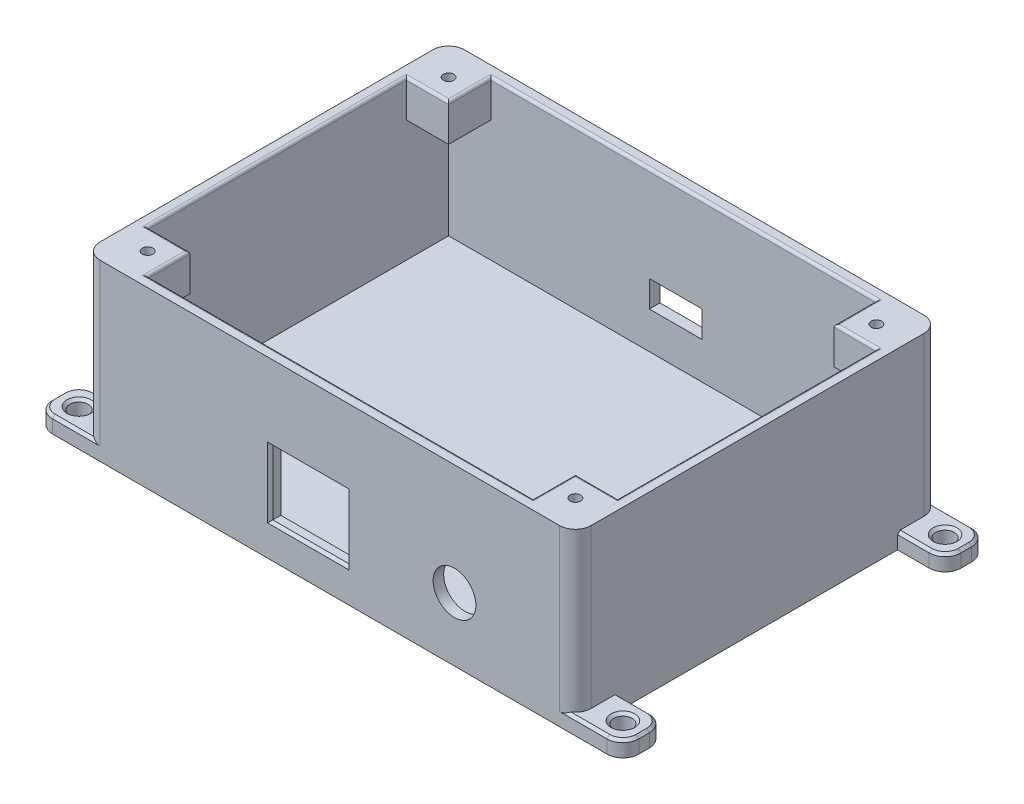
SolidWorks part; units mm, degrees
ref_plane "Front Plane" through (0, 0, 0) normal (0, 0, 1) x (1, 0, 0)
ref_plane "Top Plane" through (0, 0, 0) normal (0, 1, 0) x (1, 0, 0)
ref_plane "Right Plane" through (0, 0, 0) normal (1, 0, 0) x (0, 0, -1)
sketch "Sketch1" plane through (0, 28.7068, 0) normal (0, -1, 0) x (-1, 0, 0)
  line L0 (-31.2305, -86.7531) -> (22.7695, -86.7531) construction
  line L1 (27.7695, -88.7531) -> (-65.2305, -88.7531)
  line L2 (27.7695, -80.7531) -> (27.7695, -27.7531)
  line L3 (27.7695, -19.7531) -> (-65.2305, -19.7531)
  line L4 (-65.2305, -80.7531) -> (-65.2305, -27.7531)
  line L5 (-43.3805, -21.7531) -> (-49.7305, -21.7531) construction
  line L6 (22.7695, -86.7531) -> (22.7695, -23.7531) construction
  line L7 (-62.2305, -23.5531) -> (-62.2305, -59.7531) construction
  line L8 (-18.7305, -19.7531) -> (-18.7305, -88.7531) construction
  line L9 (27.7695, -19.7531) -> (33.7695, -19.7531)
  line L11 (27.7695, -27.7531) -> (33.7695, -27.7531)
  line L12 (36.7695, -22.7531) -> (36.7695, -24.7531)
  line L13 (-65.2305, -54.2531) -> (27.7695, -54.2531) construction
  line L14 (-74.2305, -22.7531) -> (-74.2305, -24.7531)
  line L15 (-65.2305, -27.7531) -> (-71.2305, -27.7531)
  line L16 (-65.2305, -19.7531) -> (-71.2305, -19.7531)
  line L17 (-65.2305, -88.7531) -> (-71.2305, -88.7531)
  line L18 (-65.2305, -80.7531) -> (-71.2305, -80.7531)
  line L19 (-74.2305, -85.7531) -> (-74.2305, -83.7531)
  line L20 (36.7695, -85.7531) -> (36.7695, -83.7531)
  line L21 (27.7695, -80.7531) -> (33.7695, -80.7531)
  line L22 (27.7695, -88.7531) -> (33.7695, -88.7531)
  arc A0 (33.7695, -27.7531) -> (36.7695, -24.7531) centre (33.7695, -24.7531) ccw
  arc A1 (33.7695, -19.7531) -> (36.7695, -22.7531) centre (33.7695, -22.7531) cw
  circle A2 centre (32.7695, -23.7531) radius 1.75
  circle A3 centre (-70.2305, -23.7531) radius 1.75
  arc A4 (-71.2305, -19.7531) -> (-74.2305, -22.7531) centre (-71.2305, -22.7531) ccw
  arc A5 (-71.2305, -27.7531) -> (-74.2305, -24.7531) centre (-71.2305, -24.7531) cw
  arc A6 (-71.2305, -80.7531) -> (-74.2305, -83.7531) centre (-71.2305, -83.7531) ccw
  arc A7 (-71.2305, -88.7531) -> (-74.2305, -85.7531) centre (-71.2305, -85.7531) cw
  circle A8 centre (-70.2305, -84.7531) radius 1.75
  circle A9 centre (32.7695, -84.7531) radius 1.75
  arc A10 (33.7695, -88.7531) -> (36.7695, -85.7531) centre (33.7695, -85.7531) ccw
  arc A11 (33.7695, -80.7531) -> (36.7695, -83.7531) centre (33.7695, -83.7531) cw
  point P17 (36.7695, -27.7531)
  point P20 (36.7695, -19.7531)
  point P27 (-18.7305, -58.2531)
  point P37 (-74.2305, -19.7531)
  point P38 (-74.2305, -27.7531)
  point P48 (-74.2305, -80.7531)
  point P49 (-74.2305, -88.7531)
  point P59 (36.7695, -88.7531)
  point P60 (36.7695, -80.7531)
  dimension "D7" = 3
  dimension "D8" = 3.5
  dimension "D1" = 2
  dimension "D2" = 2
  dimension "D3" = 5
  dimension "D4" = 3
  dimension "D5" = 9
  dimension "D6" = 8
  dimension "D9" = 5
extrude "Boss-Extrude1" add sketch "Sketch1" along normal blind 3
sketch "Sketch2" plane through (0, 28.7068, 0) normal (0, 1, 0) x (1, 0, 0)
  line L0 (-27.7695, -27.7531) -> (-27.7695, -19.7531) construction
  line L1 (-33.7695, -19.7531) -> (71.2305, -19.7531) construction
  line L2 (65.2305, -80.7531) -> (65.2305, -88.7531) construction
  line L3 (71.2305, -88.7531) -> (-33.7695, -88.7531) construction
  line L4 (-25.7695, -21.7531) -> (63.2305, -21.7531)
  line L5 (-27.7695, -19.7531) -> (65.2305, -19.7531)
  line L6 (-27.7695, -19.7531) -> (-27.7695, -88.7531)
  line L7 (-27.7695, -88.7531) -> (65.2305, -88.7531)
  line L8 (65.2305, -19.7531) -> (65.2305, -88.7531)
  line L9 (63.2305, -21.7531) -> (63.2305, -86.7531)
  line L10 (-25.7695, -86.7531) -> (63.2305, -86.7531)
  line L11 (-25.7695, -21.7531) -> (-25.7695, -86.7531)
  dimension "D1" = 2
extrude "Boss-Extrude2" add sketch "Sketch2" along normal blind 30
sketch "Sketch3" plane through (0, 58.7068, 0) normal (0, 1, 0) x (1, 0, 0)
  line L0 (18.7305, -21.7531) -> (18.7305, -86.7531) construction
  line L1 (-25.7695, -21.7531) -> (-17.7695, -21.7531)
  line L2 (-25.7695, -21.7531) -> (-25.7695, -29.7531)
  line L3 (-25.7695, -29.7531) -> (-17.7695, -29.7531)
  line L4 (-17.7695, -21.7531) -> (-17.7695, -29.7531)
  line L5 (63.2305, -21.7531) -> (-25.7695, -21.7531) construction
  line L6 (-25.7695, -86.7531) -> (63.2305, -86.7531) construction
  line L7 (-25.7695, -54.2531) -> (63.2305, -54.2531) construction
  line L8 (-25.7695, -21.7531) -> (-25.7695, -86.7531) construction
  line L9 (63.2305, -86.7531) -> (63.2305, -21.7531) construction
  line L10 (55.2305, -21.7531) -> (55.2305, -29.7531)
  line L11 (63.2305, -29.7531) -> (55.2305, -29.7531)
  line L12 (63.2305, -21.7531) -> (63.2305, -29.7531)
  line L13 (63.2305, -21.7531) -> (55.2305, -21.7531)
  line L14 (63.2305, -86.7531) -> (55.2305, -86.7531)
  line L15 (63.2305, -86.7531) -> (63.2305, -78.7531)
  line L16 (63.2305, -78.7531) -> (55.2305, -78.7531)
  line L17 (55.2305, -86.7531) -> (55.2305, -78.7531)
  line L18 (-17.7695, -86.7531) -> (-17.7695, -78.7531)
  line L19 (-25.7695, -78.7531) -> (-17.7695, -78.7531)
  line L20 (-25.7695, -86.7531) -> (-25.7695, -78.7531)
  line L21 (-25.7695, -86.7531) -> (-17.7695, -86.7531)
  circle A0 centre (-21.7695, -25.7531) radius 1
  circle A1 centre (59.2305, -25.7531) radius 1
  circle A2 centre (59.2305, -82.7531) radius 1
  circle A3 centre (-21.7695, -82.7531) radius 1
  dimension "D3" = 2
  dimension "D1" = 8
  dimension "D2" = 8
extrude "Boss-Extrude3" add sketch "Sketch3" against normal blind 15
chamfer "Chamfer1" distance 8 angle 45 8 edges at (-17.7695, 43.7068, 25.7531) (-21.7695, 43.7068, 29.7531) (-21.7695, 43.7068, 78.7531) (-17.7695, 43.7068, 82.7531) (55.2305, 43.7068, 82.7531) (59.2305, 43.7068, 78.7531) (59.2305, 43.7068, 29.7531) (55.2305, 43.7068, 25.7531)
sketch "Sketch4" plane through (0, 0, 19.7531) normal (0, 0, -1) x (-1, 0, 0)
  circle A0 centre (-46.5555, 33.3018) radius 3.25
  dimension "D1" = 6.5
extrude "Cut-Extrude1" cut sketch "Sketch4" against normal blind 2
sketch "Sketch5" plane through (0, 0, 88.7531) normal (0, 0, 1) x (1, 0, 0)
  line L1 (7.4479, 44.2572) -> (21.8431, 44.2572)
  line L2 (7.4479, 44.2572) -> (7.4479, 31.9874)
  line L3 (7.4479, 31.9874) -> (21.8431, 31.9874)
  line L4 (21.8431, 44.2572) -> (21.8431, 31.9874)
  line L6 (20.8431, 43.2572) -> (20.8431, 40.387) construction
  line L8 (8.4479, 40.387) -> (8.4479, 43.2572) construction
  line L9 (8.4479, 43.2572) -> (20.8431, 43.2572) construction
  line L10 (16.6775, 32.9874) -> (12.6135, 32.9874) construction
  dimension "D1" = 1
  dimension "D2" = 1
  dimension "D3" = 1
  dimension "D4" = 1
extrude "Cut-Extrude2" cut sketch "Sketch5" against normal blind 2
chamfer "Chamfer2" distance 0.5 angle 45 4 edges at (14.6455, 31.9874, 88.7531) (21.8431, 38.1223, 88.7531) (14.6455, 44.2572, 88.7531) (7.4479, 38.1223, 88.7531)
fillet "Fillet1" radius 3 4 edges at (-27.7695, 43.7068, 19.7531) (-27.7695, 43.7068, 88.7531) (65.2305, 43.7068, 88.7531) (65.2305, 43.7068, 19.7531)
chamfer "Chamfer4" distance 0.5 angle 45 24 edges at (-31.0195, 28.7068, 23.7531) (-30.7695, 28.7068, 27.7531) (-35.8908, 28.7068, 26.8745) (-36.7695, 28.7068, 23.7531) (-35.8908, 28.7068, 20.6318) (-29.2695, 28.7068, 19.7531) (68.2305, 28.7068, 27.7531) (73.3518, 28.7068, 26.8745) (74.2305, 28.7068, 23.7531) (73.3518, 28.7068, 20.6318) (66.7305, 28.7068, 19.7531) (68.4805, 28.7068, 23.7531) (71.9805, 28.7068, 84.7531) (66.7305, 28.7068, 88.7531) (73.3518, 28.7068, 87.8745) (74.2305, 28.7068, 84.7531) (73.3518, 28.7068, 81.6318) (68.2305, 28.7068, 80.7531) (-34.5195, 28.7068, 84.7531) (-29.2695, 28.7068, 88.7531) (-35.8908, 28.7068, 87.8745) (-36.7695, 28.7068, 84.7531) (-35.8908, 28.7068, 81.6318) (-30.7695, 28.7068, 80.7531)
fillet "Fillet2" radius 0.5 12 edges at (-21.7695, 58.7068, 78.7531) (-17.7695, 58.7068, 82.7531) (18.7305, 58.7068, 86.7531) (55.2305, 58.7068, 82.7531) (59.2305, 58.7068, 78.7531) (63.2305, 58.7068, 54.2531) (59.2305, 58.7068, 29.7531) (55.2305, 58.7068, 25.7531) (-21.7695, 58.7068, 29.7531) (-17.7695, 58.7068, 25.7531) (18.7305, 58.7068, 21.7531) (-25.7695, 58.7068, 54.2531)
sketch "Sketch6" plane through (0, 0, 88.7531) normal (0, 0, 1) x (1, 0, 0)
  line L0 (71.2305, 25.7068) -> (-33.7695, 25.7068) construction
  line L1 (22.3431, 44.7572) -> (22.3431, 31.4874) construction
  circle A0 centre (42.3431, 37.7068) radius 4.05
  dimension "D1" = 8.1
  dimension "D2" = 12
  dimension "D3" = 20
extrude "Cut-Extrude3" cut sketch "Sketch6" against normal blind 2
sketch "Sketch7" plane through (0, 0, 19.7531) normal (0, 0, -1) x (-1, 0, 0)
  line L0 (33.7695, 25.7068) -> (-71.2305, 25.7068) construction
  line L1 (-22.2305, 40.7068) -> (-12.2305, 40.7068)
  line L2 (-22.2305, 40.7068) -> (-22.2305, 35.7068)
  line L3 (-22.2305, 35.7068) -> (-12.2305, 35.7068)
  line L4 (-12.2305, 40.7068) -> (-12.2305, 35.7068)
  line L5 (-62.2305, 58.7068) -> (-62.2305, 28.2068) construction
  dimension "D1" = 10
  dimension "D2" = 5
  dimension "D3" = 10
  dimension "D4" = 40
extrude "Cut-Extrude4" cut sketch "Sketch7" against normal blind 2
